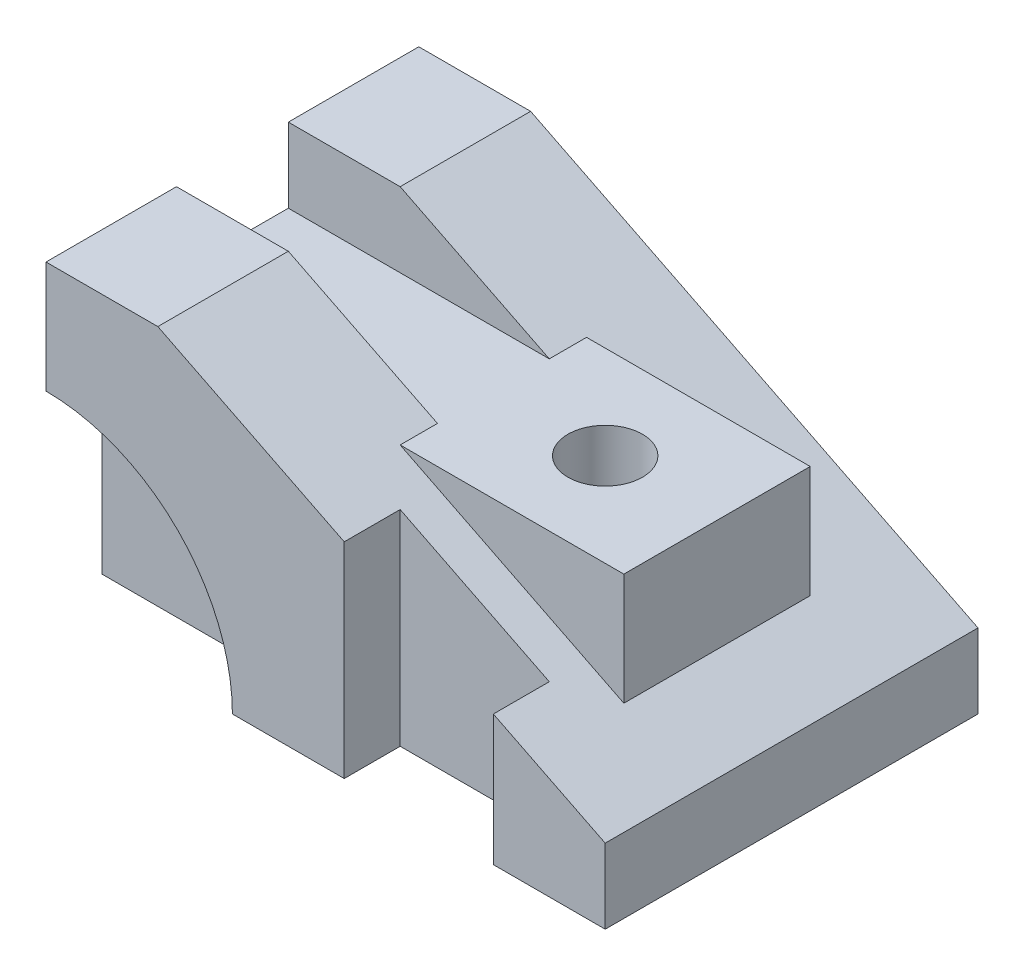
SolidWorks part; units mm, degrees
ref_plane "Front Plane" through (0, 0, 0) normal (0, 0, 1) x (1, 0, 0)
ref_plane "Top Plane" through (0, 0, 0) normal (0, 1, 0) x (1, 0, 0)
ref_plane "Right Plane" through (0, 0, 0) normal (1, 0, 0) x (0, 0, -1)
sketch "Sketch1" plane through (0, 0, 0) normal (0, 0, 1) x (1, 0, 0)
  line L0 (0, 0) -> (0, 80)
  line L1 (0, 80) -> (30, 80)
  line L2 (30, 80) -> (150, 20)
  line L3 (150, 20) -> (150, 0)
  line L4 (150, 0) -> (0, 0)
  point P4 (30, 80)
  point P7 (30, 80)
  point P8 (150, 27.6023)
  dimension "D1" = 80
  dimension "D2" = 150
  dimension "D3" = 30
  dimension "D4" = 20
extrude "Boss-Extrude1" add sketch "Sketch1" against normal blind 50 and the other way blind 50 contours L4 L0 L1 L2 L3
sketch "Sketch2" plane through (0, 0, 50) normal (0, 0, 1) x (1, 0, 0)
  circle A0 centre (0, 0) radius 50
  dimension "D1" = 100
extrude "Cut-Extrude2" cut sketch "Sketch2" against normal blind 15
sketch3d "3DSketch1" plane through (0, 0, 0) normal (0, 0, 1) x (1, 0, 0)
sketch "Sketch4" plane through (0, 0, 0) normal (0, 0, 1) x (1, 0, 0)
  line L0 (70, 60) -> (130, 60)
  line L1 (30, 80) -> (150, 20) construction
  line L2 (130, 60) -> (130, 30)
  line L3 (130, 30) -> (70, 60)
  dimension "D1" = 20
  dimension "D2" = 30
extrude "Boss-Extrude2" add sketch "Sketch4" along normal blind 25 and the other way blind 25
sketch "Sketch5" plane through (0, 60, 0) normal (0, 1, 0) x (1, 0, 0)
  line L0 (0, 50) -> (30, 50) construction
  line L1 (-23.2103, 15) -> (81.3968, 15)
  line L2 (-23.2103, 15) -> (-23.2103, -15)
  line L3 (-23.2103, -15) -> (81.3968, -15)
  line L4 (81.3968, 15) -> (81.3968, -15)
  line L5 (0, -50) -> (30, -50) construction
  dimension "D1" = 35
  dimension "D2" = 35
extrude "Cut-Extrude3" cut sketch "Sketch5" along normal blind 25
sketch "Sketch6" plane through (0, 0, 0) normal (0, -1, 0) x (1, 0, 0)
  line L0 (150, 50) -> (50, 50) construction
  line L1 (80, 50) -> (120, 50)
  line L2 (80, 50) -> (80, 35)
  line L3 (80, 35) -> (120, 35)
  line L4 (120, 50) -> (120, 35)
  line L5 (150, 50) -> (150, -50) construction
  dimension "D1" = 30
  dimension "D2" = 15
  dimension "D3" = 40
extrude "Cut-Extrude4" cut sketch "Sketch6" against normal through all
sketch "Sketch7" plane through (0, 60, 0) normal (0, 1, 0) x (1, 0, 0)
  line L0 (70, 25) -> (130, 25) construction
  line L2 (130, 25) -> (130, -25) construction
  circle A0 centre (100, 0) radius 10
  dimension "D3" = 20
  dimension "D1" = 25
  dimension "D2" = 30
extrude "Cut-Extrude5" cut sketch "Sketch7" against normal through all
